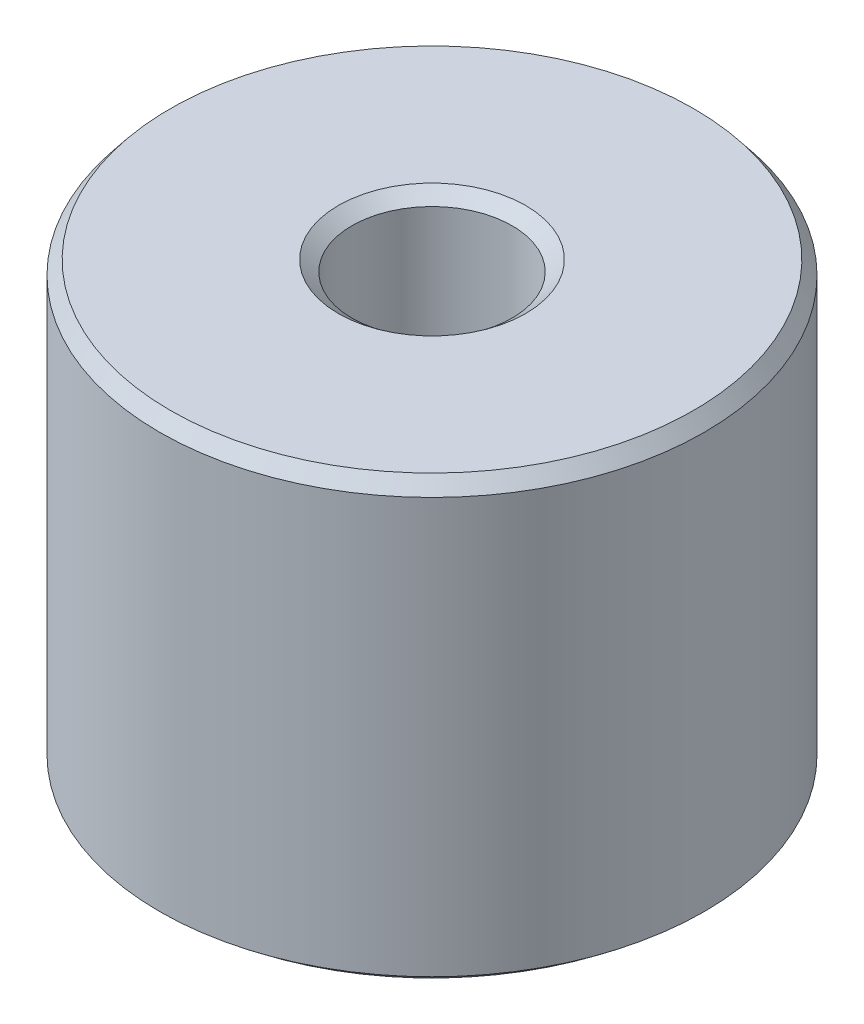
SolidWorks part; units mm, degrees
ref_plane "Front Plane" through (0, 0, 0) normal (0, 0, 1) x (1, 0, 0)
ref_plane "Top Plane" through (0, 0, 0) normal (0, 1, 0) x (1, 0, 0)
ref_plane "Right Plane" through (0, 0, 0) normal (1, 0, 0) x (0, 0, -1)
sketch "Sketch1" plane through (0, 0, 0) normal (0, 1, 0) x (1, 0, 0)
  circle A0 centre (0, 0) radius 7.5
  dimension "SLEEVE_OD" = 15
extrude "Boss-Extrude1" add sketch "Sketch1" along normal blind 12.1029
sketch "Sketch2" plane through (0, 0, 0) normal (0, 1, 0) x (1, 0, 0)
  circle A0 centre (0, 0) radius 2.2063
  dimension "BORE_D" = 4.4126
extrude "Cut-Extrude1" cut sketch "Sketch2" along normal through all
chamfer "Chamfer1" distance 0.3735 angle 38.338 4 edges at (0, 12.1029, 2.2063) (0, 0, 2.2063) (0, 0, 7.5) (0, 12.1029, 7.5) first distance on face at (0, 12.1029, 2.2063) first distance on face at (0, 0, 2.2063) first distance on face at (0, 12.1029, 7.5)
